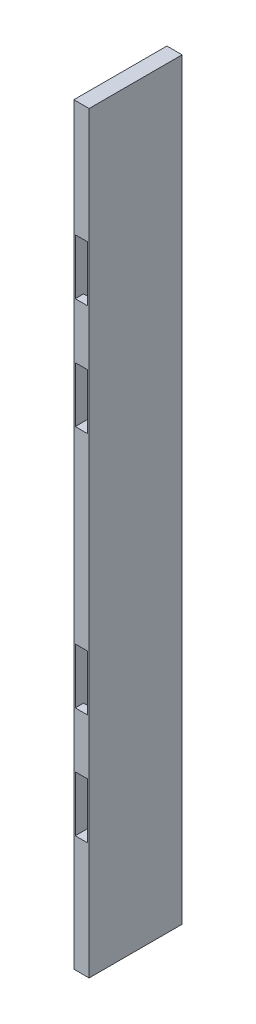
SolidWorks part; units mm, degrees
ref_plane "Top" through (0, 0, 0) normal (0, 0, 1) x (1, 0, 0)
ref_plane "Front" through (0, 0, 0) normal (0, 1, 0) x (1, 0, 0)
ref_plane "Right" through (0, 0, 0) normal (1, 0, 0) x (0, 0, -1)
sketch "Profile Sketch" plane through (0.0456, 0, -0.0242) normal (0, 1, 0) x (-1, 0, 0)
  line L0 (2.5456, -16.7758) -> (2.5456, 0.0242)
  line L1 (2.5456, 0.0242) -> (0.0456, 0.0242)
  line L2 (0.0456, 0.0242) -> (0.0456, -16.7758)
  line L3 (0.0456, -16.7758) -> (2.5456, -16.7758)
  line L12 (2.2956, 0.0242) -> (2.2956, -16.7758) construction
  dimension "D1" = 16.8
  dimension "D3" = 2.25
  dimension "Cover Thickness" = 0.25
extrude "Profile Extrude" add sketch "Profile Sketch" along normal blind 136
ref_plane "Mid Plane" through (0, 68, 0) normal (0, -1, 0) x (-1, 0, 0)
ref_plane "Right Cut Out Location" through (0, 36, 0) normal (0, -1, 0) x (-1, 0, 0)
ref_plane "Left Cut Out Location" through (0, 100, 0) normal (0, -1, 0) x (-1, 0, 0)
sketch "Cover Latch Cut Out Sketch" plane through (-2.5, 0, 0) normal (-1, 0, 0) x (0, 0, 1)
  line L0 (-16.8, 136) -> (-16.8, 0) construction
  line L4 (-16.8, 51) -> (-16.8, 21)
  line L5 (0, 31) -> (-1.5, 31)
  line L10 (0, 41) -> (0, 31) construction
  line L11 (0, 136) -> (0, 0) construction
  line L12 (-1.5, 31) -> (-2.1583, 36)
  line L13 (-2.1583, 36) -> (-1.5, 41)
  line L14 (-1.5, 41) -> (0, 41)
  line L15 (-2.1583, 36) -> (0, 36) construction
  line L16 (0, 41) -> (0, 51)
  line L17 (0, 51) -> (-16.8, 51)
  line L18 (0, 31) -> (0, 21)
  line L21 (0, 21) -> (-16.8, 21)
  point P3 (0, 68)
  dimension "D1" = 1.5
  dimension "D2" = 10
  dimension "D3" = 10
  dimension "D4" = 7.5
  dimension "Latch Position" = 32
extrude "Cover Latch Cut Out" cut sketch "Cover Latch Cut Out Sketch" against normal blind 2.25
mirror "Cover Latch Cut Out Mirror" about plane through (0, 68, 0) normal (0, -1, 0) of "Cover Latch Cut Out"
sketch "Side Sketch" plane through (0, 0, 0) normal (0, 1, 0) x (1, 0, 0)
  line L7 (-2.75, 16.8) -> (-2.5, 16.8)
  line L8 (-2.75, 16.8) -> (-2.75, 0)
  line L9 (-2.75, 0) -> (-2.5, 0)
  line L10 (-2.5, 16.8) -> (-2.5, 0)
  dimension "Cover Thickness" = 0.25
extrude "Side Extrude" add sketch "Side Sketch" along normal through all
